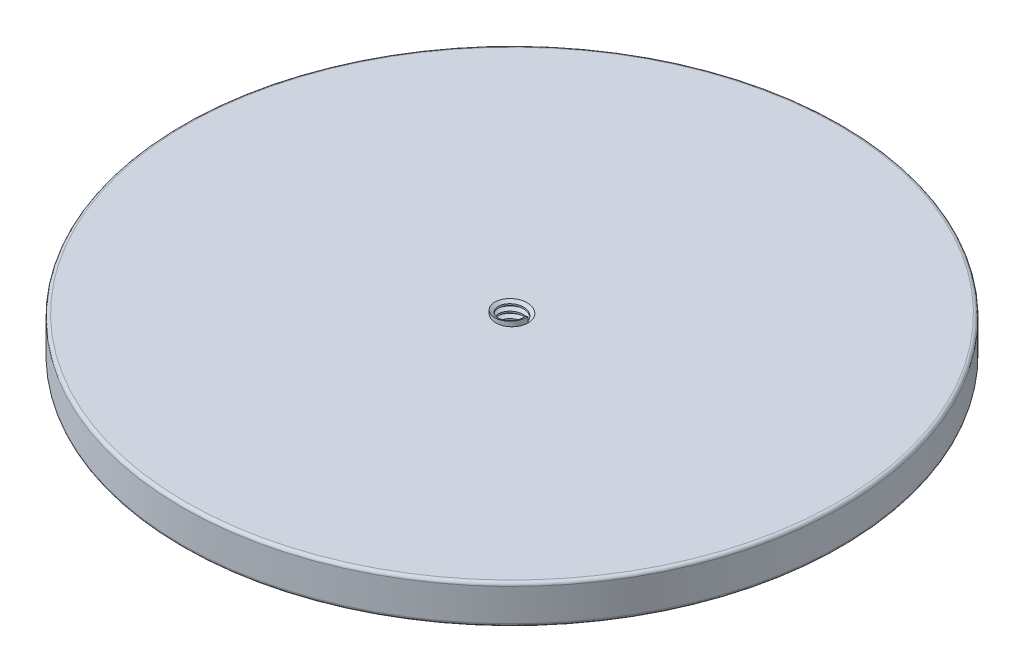
SolidWorks part; units mm, degrees
ref_plane "Front" through (0, 0, 0) normal (0, 0, 1) x (1, 0, 0)
ref_plane "Top" through (0, 0, 0) normal (0, 1, 0) x (1, 0, 0)
ref_plane "Right" through (0, 0, 0) normal (1, 0, 0) x (0, 0, -1)
sketch "Sketch2" plane through (0, 0, 0) normal (0, 1, 0) x (1, 0, 0)
  circle A0 centre (0, 0) radius 64.77
  dimension "D1" = 129.54
extrude "Boss-Extrude1" add sketch "Sketch2" against normal blind 7.62
fillet "Fillet1" radius 0.635 2 edges at (0, -7.62, 64.77) (0, 0, 64.77)
sketch "Sketch3" plane through (0, 0, 0) normal (0, 1, 0) x (1, 0, 0)
  circle A0 centre (0, 0) radius 28.448
  dimension "D1" = 56.896
extrude "Boss-Extrude2" add sketch "Sketch3" against normal blind 12.7 from surface starting at face at (0, -7.62, 64.135)
fillet "Fillet2" radius 0.635 1 edges at (0, -20.32, 28.448)
sketch "Sketch4" plane through (0, -20.32, 0) normal (0, -1, 0) x (1, 0, 0)
  circle A0 centre (0, 0) radius 3.175
  dimension "D1" = 6.35
extrude "Cut-Extrude1" cut sketch "Sketch4" against normal through all
thread "Thread1" pitch 1.27 method extrude profile "Thread Profile1" start angle 0, offset 0, length 0, pitch 1.27, diameter 6.35
ref_plane "Plane1" through (3.175, -20.32, 0) normal (0, 0, 1) x (1, 0, 0)
sketch "Thread Profile1" plane through (3.175, -20.32, 0) normal (0, 0, 1) x (1, 0, 0)
  line L0 (0, 0) -> (0, 1.27) construction
  line L11 (0, 0) -> (0, 1.1112)
  line L12 (0, 1.1112) -> (-0.6874, 0.7144)
  line L13 (-0.6874, 0.7144) -> (-0.6874, 0.3969)
  line L15 (-0.6874, 0.3969) -> (0, 0)
  line L17 (-0.6874, 0.5556) -> (0, 0.5556) construction
  point P2 (0, 0)
  dimension "Pitch" = 1.27
  dimension "Profile_Angle" = 60
  dimension "Profile_Land" = 0.3175
  dimension "Profile_Height" = 0.6874
